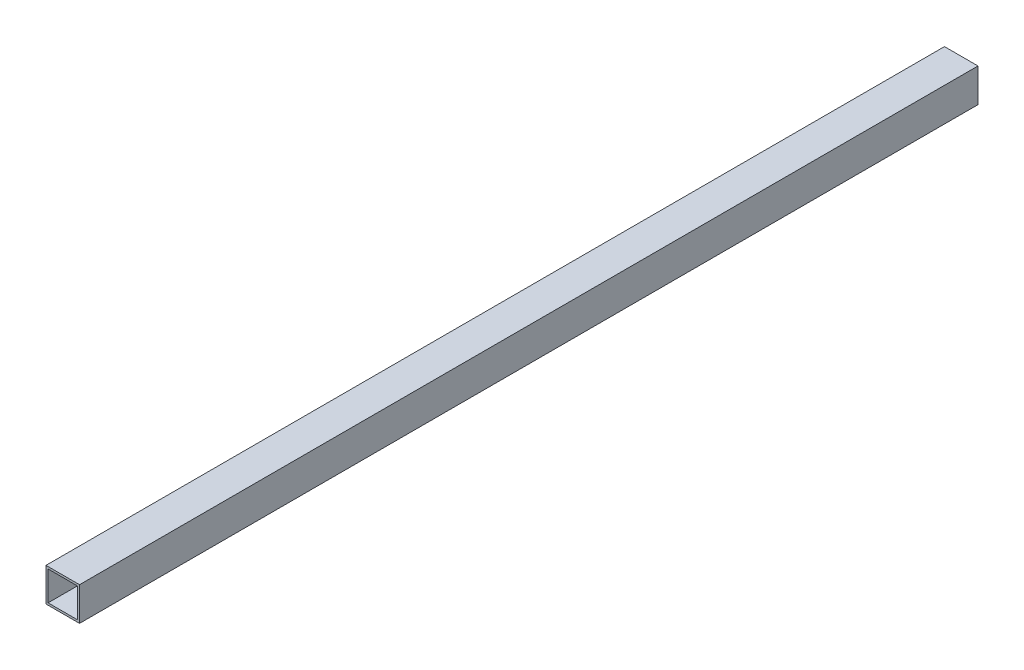
SolidWorks part; units mm, degrees
material "ALUMINUM 6061-T6"
ref_plane "Front Plane" through (0, 0, 0) normal (0, 0, 1) x (1, 0, 0)
ref_plane "Top Plane" through (0, 0, 0) normal (0, 1, 0) x (1, 0, 0)
ref_plane "Right Plane" through (0, 0, 0) normal (1, 0, 0) x (0, 0, -1)
sketch "Sketch1" plane through (0, 0, 0) normal (0, 0, 1) x (1, 0, 0)
  line L1 (-12.7, -12.7) -> (12.7, -12.7)
  line L2 (-12.7, -12.7) -> (-12.7, 12.7)
  line L3 (-12.7, 12.7) -> (12.7, 12.7)
  line L4 (12.7, -12.7) -> (12.7, 12.7)
  line L5 (-12.7, -12.7) -> (12.7, 12.7) construction
  line L6 (-12.7, 12.7) -> (12.7, -12.7) construction
  point P0 (0, 0)
  dimension "D1" = 25.4
  dimension "D2" = 25.4
extrude "Boss-Extrude1" add sketch "Sketch1" along normal mid plane 680.72
sketch "Sketch2" plane through (0, 0, 340.36) normal (0, 0, 1) x (1, 0, 0)
  line L0 (-11.1125, 11.1125) -> (-11.1125, -11.1125)
  line L1 (-12.7, 12.7) -> (12.7, 12.7)
  line L2 (-12.7, 12.7) -> (-12.7, -12.7)
  line L3 (-12.7, -12.7) -> (12.7, -12.7)
  line L4 (12.7, 12.7) -> (12.7, -12.7)
  line L5 (-11.1125, -11.1125) -> (11.1125, -11.1125)
  line L6 (11.1125, 11.1125) -> (11.1125, -11.1125)
  line L7 (-11.1125, 11.1125) -> (11.1125, 11.1125)
  dimension "D1" = 1.5875
extrude "Cut-Extrude1" cut sketch "Sketch2" against normal through all contours L7 L6 L5 L0
